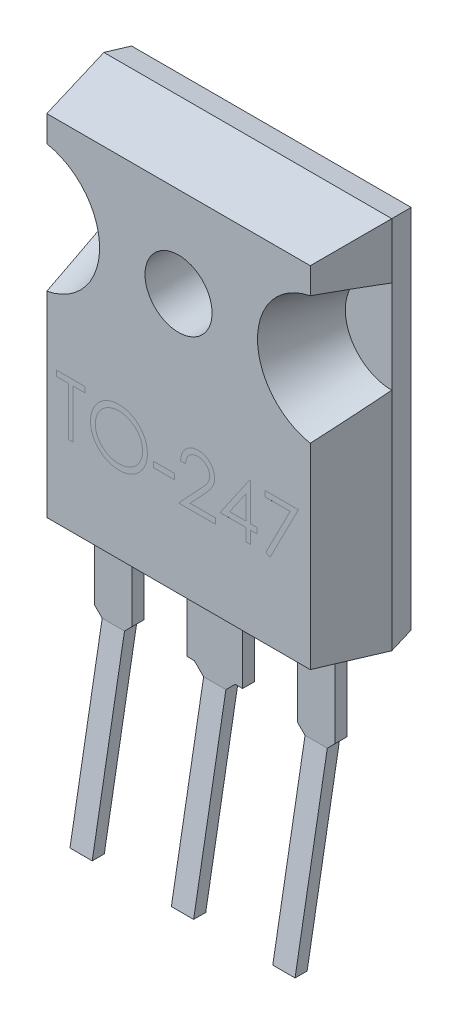
SolidWorks part; units mm, degrees
ref_plane "Front Plane" through (0, 0, 0) normal (0, 0, 1) x (1, 0, 0)
ref_plane "Top Plane" through (0, 0, 0) normal (0, 1, 0) x (1, 0, 0)
ref_plane "Right Plane" through (0, 0, 0) normal (1, 0, 0) x (0, 0, -1)
sketch "Sketch1" plane through (0, 0, 0) normal (0, 0, 1) x (1, 0, 0)
  line L1 (-7.75, 10.075) -> (7.75, 10.075)
  line L2 (-7.75, 10.075) -> (-7.75, -10.075)
  line L3 (-7.75, -10.075) -> (7.75, -10.075)
  line L4 (7.75, 10.075) -> (7.75, -10.075)
  line L5 (-7.75, 10.075) -> (7.75, -10.075) construction
  line L6 (-7.75, -10.075) -> (7.75, 10.075) construction
  point P0 (0, 0)
  dimension "D1" = 15.5
  dimension "D2" = 20.15
extrude "Boss-Extrude1" add sketch "Sketch1" against normal blind 1.27 draft 10 and the other way blind 3.73 draft 10
sketch "Sketch2" plane through (0, 0, 0) normal (0, 0, 1) x (1, 0, 0)
  line L0 (7.75, 10.075) -> (-7.75, 10.075) construction
  line L1 (-5.25, 7.4139) -> (-5.25, 0.8413) construction
  line L2 (-7.75, 10.075) -> (-7.75, -10.075) construction
  line L3 (0, 14.1994) -> (0, -3.2617) construction
  line L4 (7.75, -10.075) -> (7.75, 10.075) construction
  circle A0 centre (0, 4.565) radius 1.805 construction
  circle A1 centre (-7.75, 4.575) radius 2.5
  circle A2 centre (7.75, 4.575) radius 2.5
  dimension "D1" = 5.51
  dimension "D2" = 3.61
  dimension "D3" = 5.5
  dimension "D4" = 5
  dimension "D5" = 2.5
  dimension "D6" = 7.75
extrude "Cut-Extrude1" cut sketch "Sketch2" along normal up to surface (3.73 mm away) draft 15
sketch "Sketch4" plane through (0, 0, 0) normal (0, 0, 1) x (1, 0, 0)
  line L0 (7.75, 10.075) -> (-7.75, 10.075) construction
  circle A0 centre (0, 4.565) radius 1.805
  dimension "D1" = 3.61
  dimension "D2" = 5.51
extrude "Cut-Extrude2" cut sketch "Sketch4" along normal through all both and the other way through all
sketch "Sketch5" plane through (0, 0, 0) normal (0, 1, 0) x (1, 0, 0)
  line L0 (-9.5483, -1.13) -> (8.845, -1.13) construction
  line L1 (7.5261, 1.27) -> (-7.5261, 1.27) construction
  line L2 (0, 2.9425) -> (0, -4.6836) construction
  line L3 (-6.47, -1.13) -> (-4.45, -1.13)
  line L4 (-6.47, -1.13) -> (-6.47, -1.78)
  line L5 (-6.47, -1.78) -> (-4.45, -1.78)
  line L6 (-4.45, -1.13) -> (-4.45, -1.78)
  line L7 (-5.46, -1.13) -> (-5.46, -1.78) construction
  line L8 (6.47, -1.13) -> (6.47, -1.78)
  line L9 (6.47, -1.13) -> (4.45, -1.13)
  line L10 (4.45, -1.13) -> (4.45, -1.78)
  line L11 (6.47, -1.78) -> (4.45, -1.78)
  line L13 (-1.5, -1.13) -> (1.5, -1.13)
  line L14 (-1.5, -1.13) -> (-1.5, -1.78)
  line L15 (-1.5, -1.78) -> (1.5, -1.78)
  line L16 (1.5, -1.13) -> (1.5, -1.78)
  point P21 (0, -1.13)
  dimension "D1" = 2.4
  dimension "D2" = 2.02
  dimension "D3" = 0.65
  dimension "D4" = 5.46
  dimension "D5" = 3
extrude "Boss-Extrude2" add sketch "Sketch5" against normal blind 14.07
sketch "Sketch6" plane through (0, 0, 1.78) normal (0, 0, 1) x (1, 0, 0)
  line L0 (1.5, -14.07) -> (-6.47, -14.07)
  line L1 (-6.47, -14.07) -> (-6.47, -11.9156)
  line L2 (-6.47, -14.07) -> (-6.47, -9.7611) construction
  line L3 (-6.47, -11.9156) -> (1.5, -11.9156)
  line L4 (1.5, -14.07) -> (1.5, -9.7611) construction
  line L5 (1.5, -11.9156) -> (1.5, -14.07)
extrude "Boss-Extrude3" add sketch "Sketch6" against normal up to surface (0.65 mm away) up to face at (-5.46, -11.9729, 1.13)
sketch "Sketch7" plane through (0, 0, -1.27) normal (0, 0, -1) x (-1, 0, 0)
  line L0 (-7.75, 10.075) -> (7.75, 10.075) construction
  line L1 (-5.9, 9.225) -> (5.9, 9.225)
  line L2 (-6.9, 8.225) -> (-6.9, -3.855)
  line L3 (-6.9, -3.855) -> (6.9, -3.855)
  line L4 (6.9, 8.225) -> (6.9, -3.855)
  line L5 (-6.9, 9.225) -> (6.9, -3.855) construction
  line L6 (-6.9, -3.855) -> (6.9, 9.225) construction
  line L7 (7.75, 7.075) -> (7.75, 2.075) construction
  circle A0 centre (0, 4.565) radius 1.805 construction
  circle A1 centre (0, 4.565) radius 1.805
  arc A2 (-6.9, 8.225) -> (-5.9, 9.225) centre (-5.9, 8.225) cw
  arc A3 (6.9, 8.225) -> (5.9, 9.225) centre (5.9, 8.225) ccw
  point P0 (0, 2.685)
  dimension "D4" = 1
  dimension "D1" = 13.08
  dimension "D2" = 0.85
  dimension "D3" = 0.85
extrude "Boss-Extrude4" add sketch "Sketch7" along normal blind 0.0001
sketch "Sketch8" plane through (0, 0, 1.78) normal (0, 0, 1) x (1, 0, 0)
  line L0 (-6.06, -14.07) -> (-6.06, -24.1858)
  line L1 (-6.47, -14.07) -> (1.5, -14.07) construction
  line L2 (-6.06, -24.1858) -> (-5.46, -25.225)
  line L3 (-5.46, -25.225) -> (-4.86, -24.1858)
  line L4 (-4.86, -24.1858) -> (-4.86, -14.07)
  line L5 (-7.75, -10.075) -> (7.75, -10.075) construction
  line L6 (-5.46, -9.7611) -> (-5.46, -27.3304) construction
  line L7 (-6.47, -9.7611) -> (-4.45, -9.7611) construction
  line L8 (0, -9.7611) -> (0, -26.1766) construction
  line L9 (-1.5, -9.7611) -> (1.5, -9.7611) construction
  line L10 (-6.06, -14.07) -> (-4.86, -14.07)
  line L11 (6.06, -14.07) -> (6.06, -24.1858)
  line L12 (6.06, -24.1858) -> (5.46, -25.225)
  line L13 (5.46, -25.225) -> (4.86, -24.1858)
  line L14 (4.86, -24.1858) -> (4.86, -14.07)
  line L15 (6.06, -14.07) -> (4.86, -14.07)
  line L16 (-0.6, -14.07) -> (-0.6, -24.1858)
  line L17 (-0.6, -24.1858) -> (0, -25.225)
  line L18 (0, -25.225) -> (0.6, -24.1858)
  line L19 (0.6, -24.1858) -> (0.6, -14.07)
  line L20 (-0.6, -14.07) -> (0.6, -14.07)
  point P28 (0, -14.07)
  dimension "D1" = 15.15
  dimension "D2" = 1.2
  dimension "D3" = 60
  dimension "D4" = 1.2
  dimension "D5" = 60
extrude "Boss-Extrude5" add sketch "Sketch8" against normal up to surface (0.65 mm away) up to face at (5.46, -11.9729, 1.13)
sketch "Sketch9" plane through (0, 0, 1.78) normal (0, 0, 1) x (1, 0, 0)
  line L0 (-1.5, -11.9156) -> (-1.5, -14.07)
  line L1 (0.6, -14.07) -> (1.5, -14.07) construction
  line L2 (-1.5, -11.9156) -> (-4.45, -11.9156)
  line L3 (-4.45, -11.9156) -> (-4.45, -14.07)
  line L4 (-4.45, -14.07) -> (-4.45, -14.32)
  line L5 (-4.45, -14.32) -> (-1.5, -14.32)
  line L6 (-1.5, -14.32) -> (-1.5, -14.07)
extrude "Cut-Extrude3" cut sketch "Sketch9" against normal blind 1
chamfer "Chamfer1" distance 0.5 angle 45 10 edges at (-4.86, -14.07, 1.455) (-6.06, -14.07, 1.455) (0.6, -14.07, 1.455) (-0.6, -14.07, 1.455) (6.06, -14.07, 1.455) (4.86, -14.07, 1.455) (-4.45, -14.07, 1.455) (-6.47, -14.07, 1.455) (6.47, -14.07, 1.455) (4.45, -14.07, 1.455)
sketch "Sketch10" plane through (0, 0, 3.73) normal (0, 0, 1) x (1, 0, 0)
  line L0 (-7.0923, -5.1918) -> (7.0923, -5.1918) construction
  line L1 (-7.0923, 1.1379) -> (-7.0923, -9.4173) construction
  line L2 (7.0923, -9.4173) -> (7.0923, 1.1379) construction
  text T0 "TO-247" font "Century Gothic" height in points 11
extrude "Cut-Extrude4" cut sketch "Sketch10" against normal blind 0.0001
sketch "Sketch11" plane through (0, 0, 0) normal (0, 0, 1) x (1, 0, 0)
  line L0 (6.06, -24.1858) -> (6.06, -14.57) construction
  line L1 (-6.06, -14.57) -> (6.06, -14.57)
  line L2 (-6.06, -14.57) -> (-6.06, -25.225)
  line L3 (-6.06, -25.225) -> (6.06, -25.225)
  line L4 (6.06, -14.57) -> (6.06, -25.225)
extrude "Cut-Extrude5" cut sketch "Sketch11" against normal through all both and the other way through all
sketch "Sketch13" plane through (0, -14.57, 0) normal (0, -1, 0) x (1, 0, 0)
  line L0 (4.86, 1.13) -> (6.06, 1.13) construction
  line L1 (6.06, 1.13) -> (6.06, 1.78) construction
  line L2 (6.06, 1.78) -> (4.86, 1.78) construction
  line L3 (4.86, 1.78) -> (4.86, 1.13) construction
  line L4 (-6.06, 1.13) -> (-4.86, 1.13) construction
  line L5 (-4.86, 1.13) -> (-4.86, 1.78) construction
  line L6 (-4.86, 1.78) -> (-6.06, 1.78) construction
  line L7 (-6.06, 1.78) -> (-6.06, 1.13) construction
  line L8 (0.6, 1.78) -> (-0.6, 1.78) construction
  line L9 (-0.6, 1.78) -> (-0.6, 1.13) construction
  line L10 (-0.6, 1.13) -> (0.6, 1.13) construction
  line L11 (0.6, 1.13) -> (0.6, 1.78) construction
  line L12 (4.86, 1.13) -> (6.06, 1.13)
  line L13 (6.06, 1.13) -> (6.06, 1.78)
  line L14 (6.06, 1.78) -> (4.86, 1.78)
  line L15 (4.86, 1.78) -> (4.86, 1.13)
  line L16 (-6.06, 1.13) -> (-4.86, 1.13)
  line L17 (-4.86, 1.13) -> (-4.86, 1.78)
  line L18 (-4.86, 1.78) -> (-6.06, 1.78)
  line L19 (-6.06, 1.78) -> (-6.06, 1.13)
  line L20 (0.6, 1.78) -> (-0.6, 1.78)
  line L21 (-0.6, 1.78) -> (-0.6, 1.13)
  line L22 (-0.6, 1.13) -> (0.6, 1.13)
  line L23 (0.6, 1.13) -> (0.6, 1.78)
sketch "Sketch12" plane through (0, 0, 0) normal (1, 0, 0) x (0, 0, -1)
  line L0 (-1.455, -14.57) -> (-3.1915, -24.4181)
  line L1 (-1.13, -14.57) -> (-1.78, -14.57) construction
  line L2 (-1.455, -14.57) -> (-1.455, -26.3136) construction
  dimension "D1" = 10
  dimension "D2" = 10
extrude "Boss-Extrude7" add sketch "Sketch13" along direction (0, -0.9848, 0.1736) on the side of the normal blind 10
